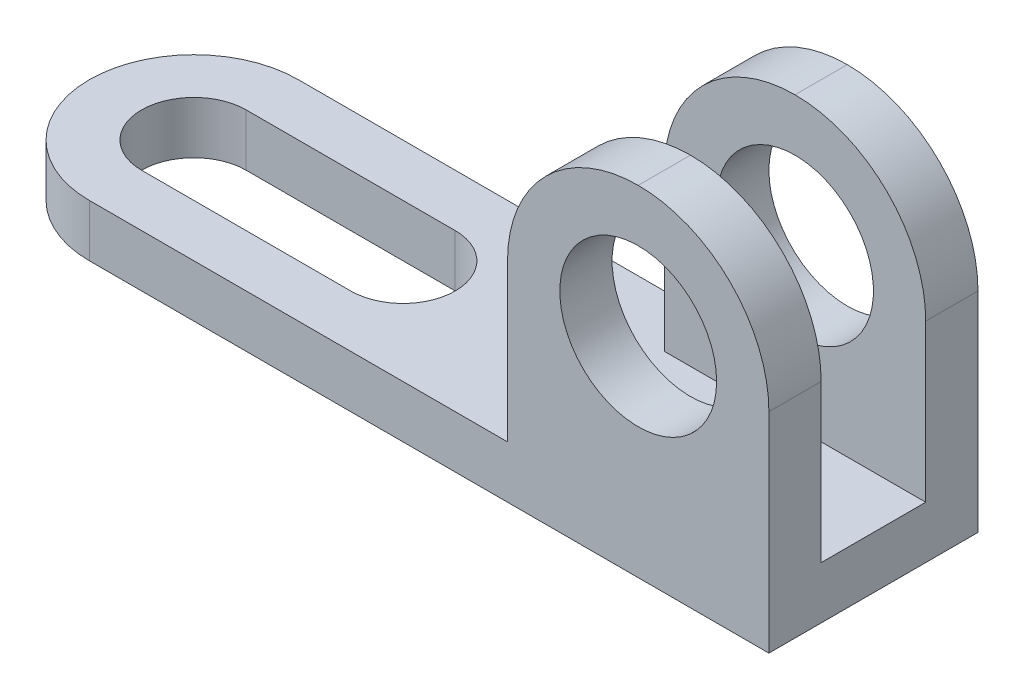
SolidWorks part; units mm, degrees
ref_plane "Front Plane" through (0, 0, 0) normal (0, 0, 1) x (1, 0, 0)
ref_plane "Top Plane" through (0, 0, 0) normal (0, 1, 0) x (1, 0, 0)
ref_plane "Right Plane" through (0, 0, 0) normal (1, 0, 0) x (0, 0, -1)
sketch "Sketch2" plane through (0, 0, 0) normal (0, 1, 0) x (1, 0, 0)
  line L1 (-75, 20) -> (75, 20)
  line L2 (-75, 20) -> (-75, -20)
  line L3 (-75, -20) -> (75, -20)
  line L4 (75, 20) -> (75, -20)
  line L5 (-75, 20) -> (75, -20) construction
  line L6 (-75, -20) -> (75, 20) construction
  point P0 (0, 0)
  dimension "D1" = 150
  dimension "D2" = 40
extrude "Boss-Extrude1" add sketch "Sketch2" along normal blind 10
sketch "Sketch9" plane through (0, 10, 0) normal (0, 1, 0) x (1, 0, 0)
  line L0 (-55, 0) -> (-15, 0) construction
  line L1 (-55, 10) -> (-15, 10)
  line L2 (-55, -10) -> (-15, -10)
  line L3 (-75, 20) -> (-75, -20) construction
  line L4 (-15, 0) -> (50, 0) construction
  arc A0 (-55, 10) -> (-55, -10) centre (-55, 0) ccw
  arc A1 (-15, -10) -> (-15, 10) centre (-15, 0) ccw
  point P3 (-35, 0)
  dimension "D1" = 10
  dimension "D2" = 20
  dimension "D3" = 40
  dimension "D4" = 65
fillet "Fillet2" radius 20 2 edges at (-75, 5, 20) (-75, 5, -20)
sketch "Sketch10" plane through (0, 10, 0) normal (0, 1, 0) x (1, 0, 0)
  line L1 (75, -20) -> (25, -20)
  line L2 (75, -20) -> (75, -10)
  line L3 (75, -10) -> (25, -10)
  line L4 (25, -20) -> (25, -10)
  dimension "D1" = 50
  dimension "D2" = 10
extrude "Boss-Extrude4" add sketch "Sketch10" along normal blind 55
sketch "Sketch12" plane through (0, 0, 20) normal (0, 0, 1) x (1, 0, 0)
  line L0 (-15, 10) -> (50, 10) construction
  circle A0 centre (50, 40) radius 15
  dimension "D1" = 30
  dimension "D2" = 30
extrude "Cut-Extrude2" cut sketch "Sketch12" against normal up to surface (10 mm away) up to face at (50, 37.5, 10)
fillet "Fillet3" radius 25 2 edges at (75, 65, 15) (25, 65, 15)
mirror "Mirror1" about plane through (0, 0, 0) normal (0, 0, 1) of "Boss-Extrude4", "Boss-Extrude1", "Fillet3"
mirror "Mirror2" about plane through (0, 0, 0) normal (0, 0, 1) of "Cut-Extrude2"
fillet "Fillet4" radius 20 2 edges at (-75, 5, 20) (-75, 5, -20)
extrude "Cut-Extrude4" cut sketch "Sketch9" against normal up to surface (10 mm away) up to face at (-8.6569, 0, 0)
